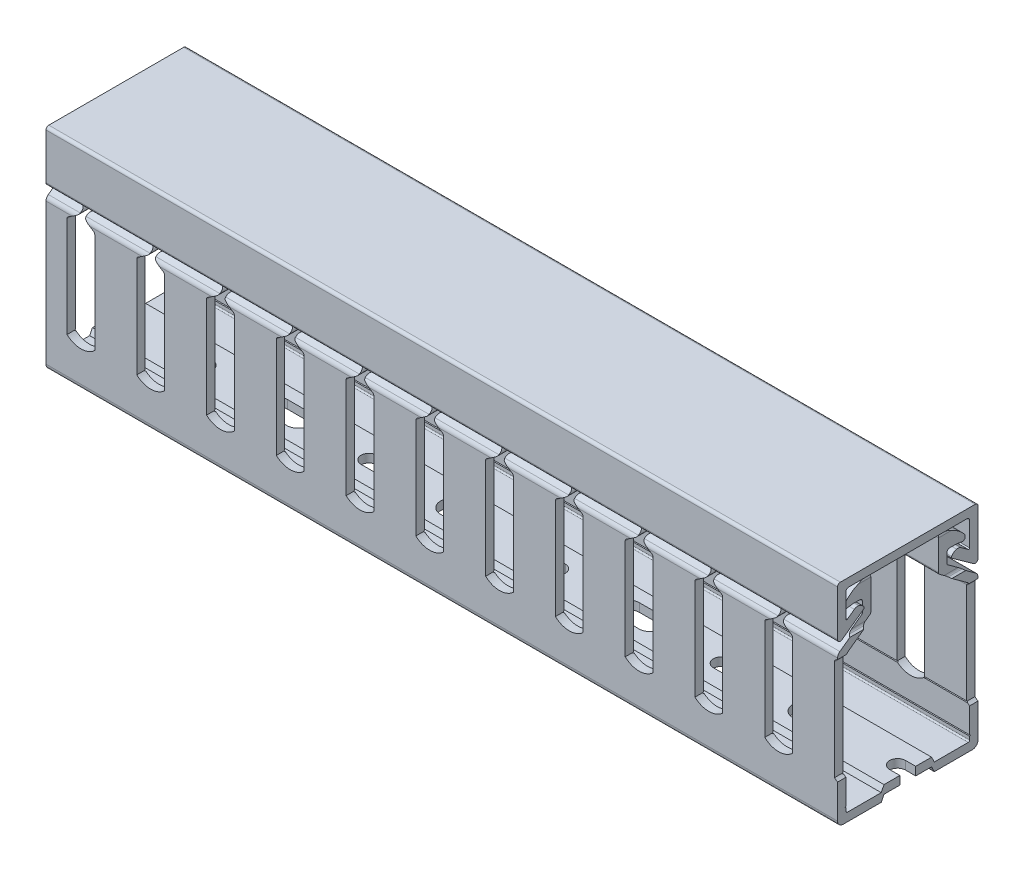
SolidWorks part; units mm, degrees
ref_plane "Alzado" through (0, 0, 0) normal (0, 0, 1) x (1, 0, 0)
ref_plane "Planta" through (0, 0, 0) normal (0, 1, 0) x (1, 0, 0)
ref_plane "Vista lateral" through (0, 0, 0) normal (1, 0, 0) x (0, 0, -1)
sketch "Croquis1" plane through (0, 0, 0) normal (1, 0, 0) x (0, 0, -1)
  line L0 (19.2861, 41.3685) -> (12.1583, 46.5609)
  line L1 (16.9056, 40.2266) -> (9.9464, 45.2924)
  line L2 (17.1611, 50.9204) -> (17.1611, 50.9657)
  line L3 (-7.5409, 0.7912) -> (-6.7469, 2.38)
  line L4 (-6.7469, 2.38) -> (-3.175, 2.38)
  line L5 (-7.5413, -1.5888) -> (-6.7469, 0)
  line L6 (-6.7469, 0) -> (-3.175, 0)
  line L7 (-7.5413, -1.5888) -> (-18.3513, -1.5888)
  line L8 (-3.175, 2.38) -> (3.175, 2.38)
  line L9 (-3.175, 0) -> (3.175, 0)
  line L10 (-17.5588, 10.0456) -> (-17.5588, 2.4512)
  line L11 (-17.162, 0.7912) -> (-7.5409, 0.7912)
  line L12 (-17.856, 2.2796) -> (-17.5588, 2.4512)
  line L13 (-17.856, 2.2796) -> (-17.5588, 2.1081)
  line L14 (-17.5588, 2.1081) -> (-17.5588, 1.1881)
  line L15 (-17.856, 10.2171) -> (-17.5588, 10.0456)
  line L16 (-17.856, 10.2171) -> (-17.5588, 10.3887)
  line L17 (17.5588, 10.0456) -> (17.5588, 2.4512)
  line L18 (17.5588, 2.1081) -> (17.5588, 1.1881)
  line L19 (17.856, 2.2796) -> (17.5588, 2.1081)
  line L20 (17.856, 2.2796) -> (17.5588, 2.4512)
  line L21 (17.856, 10.2171) -> (17.5588, 10.3887)
  line L22 (17.856, 10.2171) -> (17.5588, 10.0456)
  line L23 (17.5588, 38.9431) -> (17.5588, 10.3887)
  line L24 (19.9388, -0.0013) -> (19.9388, 40.0854)
  line L25 (12.0017, 46.8688) -> (12.0017, 49.624)
  line L26 (9.6198, 45.9342) -> (9.6198, 54.439)
  line L27 (14.842, 50.4074) -> (16.2738, 50.1687)
  line L28 (12.7954, 50.4177) -> (14.7167, 50.4177)
  line L29 (-19.2861, 41.3685) -> (-12.1583, 46.5609)
  line L30 (-16.9056, 40.2266) -> (-9.9464, 45.2924)
  line L31 (-9.6198, 45.9342) -> (-9.6198, 54.439)
  line L32 (-12.7954, 50.4177) -> (-14.7167, 50.4177)
  line L33 (-12.0017, 46.8688) -> (-12.0017, 49.624)
  line L34 (-14.842, 50.4074) -> (-16.2738, 50.1687)
  line L35 (-17.1611, 50.9204) -> (-17.1611, 50.9657)
  line L36 (-17.5588, 38.9431) -> (-17.5588, 10.3887)
  line L37 (-19.9388, -0.0013) -> (-19.9388, 40.0854)
  line L38 (3.175, 0) -> (6.7469, 0)
  line L39 (6.7469, 0) -> (7.5413, -1.5888)
  line L40 (7.5413, -1.5888) -> (18.3513, -1.5888)
  line L41 (17.162, 0.7912) -> (7.5413, 0.7912)
  line L42 (7.5413, 0.7912) -> (6.7469, 2.38)
  line L43 (6.7469, 2.38) -> (3.175, 2.38)
  arc A0 (-17.5588, 1.1881) -> (-17.162, 0.7912) centre (-17.162, 1.1881) ccw
  arc A1 (-19.9388, -0.0013) -> (-18.3513, -1.5888) centre (-18.3513, -0.0013) ccw
  arc A2 (17.162, 0.7912) -> (17.5588, 1.1881) centre (17.162, 1.1881) ccw
  arc A3 (18.3513, -1.5888) -> (19.9388, -0.0013) centre (18.3513, -0.0013) ccw
  arc A4 (19.9388, 40.0854) -> (19.2861, 41.3685) centre (18.3513, 40.0854) ccw
  arc A5 (17.5588, 38.9431) -> (16.9056, 40.2266) centre (15.9713, 38.9431) ccw
  arc A6 (12.0017, 46.8688) -> (12.1583, 46.5609) centre (12.3827, 46.8688) ccw
  arc A7 (9.6198, 45.9342) -> (9.9464, 45.2924) centre (10.4136, 45.9342) ccw
  arc A8 (12.7954, 50.4177) -> (12.0017, 49.624) centre (12.7954, 49.624) ccw
  arc A9 (10.688, 55.1838) -> (9.6198, 54.439) centre (10.4136, 54.439) ccw
  arc A10 (16.86, 51.7867) -> (10.688, 55.1838) centre (9.3251, 45.4023) ccw
  arc A11 (17.1611, 50.9657) -> (16.86, 51.7867) centre (15.8911, 50.9657) ccw
  arc A12 (16.2738, 50.1687) -> (17.1611, 50.9204) centre (16.3991, 50.9204) ccw
  arc A13 (14.842, 50.4074) -> (14.7167, 50.4177) centre (14.7167, 49.6557) ccw
  arc A14 (-9.9464, 45.2924) -> (-9.6198, 45.9342) centre (-10.4136, 45.9342) ccw
  arc A15 (-16.9056, 40.2266) -> (-17.5588, 38.9431) centre (-15.9713, 38.9431) ccw
  arc A16 (-19.2861, 41.3685) -> (-19.9388, 40.0854) centre (-18.3513, 40.0854) ccw
  arc A17 (-9.6198, 54.439) -> (-10.688, 55.1838) centre (-10.4136, 54.439) ccw
  arc A18 (-16.86, 51.7867) -> (-17.1611, 50.9657) centre (-15.8911, 50.9657) ccw
  arc A19 (-12.1583, 46.5609) -> (-12.0017, 46.8688) centre (-12.3827, 46.8688) ccw
  arc A20 (-12.0017, 49.624) -> (-12.7954, 50.4177) centre (-12.7954, 49.624) ccw
  arc A21 (-14.7167, 50.4177) -> (-14.842, 50.4074) centre (-14.7167, 49.6557) ccw
  arc A22 (-17.1611, 50.9204) -> (-16.2738, 50.1687) centre (-16.3991, 50.9204) ccw
  arc A23 (-10.688, 55.1838) -> (-16.86, 51.7867) centre (-9.3251, 45.4023) ccw
  point P92 (0, 0)
extrude "Saliente-Extruir1" add sketch "Croquis1" along normal mid plane 762
sketch "Croquis5" plane through (0, 2.38, 0) normal (0, 1, 0) x (1, 0, 0)
  line L157 (-379.0156, -3.2514) -> (-381, -3.2514)
  line L158 (-379.0156, 3.251) -> (-381, 3.251)
  line L159 (-335.6864, 3.251) -> (-329.3364, 3.251)
  line L160 (-335.6864, -3.2514) -> (-329.3364, -3.2514)
  line L161 (-235.6612, -3.2514) -> (-229.3112, -3.2514)
  line L162 (-235.6612, 3.251) -> (-229.3112, 3.251)
  line L163 (-285.6738, -3.2514) -> (-279.3238, -3.2514)
  line L164 (-285.6738, 3.251) -> (-279.3238, 3.251)
  line L165 (-185.6486, -3.2514) -> (-179.2986, -3.2514)
  line L166 (-185.6486, 3.251) -> (-182.1992, 3.251)
  line L167 (-309.2402, 2.2477) -> (-305.7446, 2.2477)
  line L168 (-309.2402, -2.2481) -> (-305.7446, -2.2481)
  line L169 (-355.7826, -2.2481) -> (-359.2782, -2.2481)
  line L170 (-355.7826, 2.2477) -> (-359.2782, 2.2477)
  line L171 (-259.2276, -2.2481) -> (-255.732, -2.2481)
  line L172 (-259.2276, 2.2477) -> (-255.732, 2.2477)
  line L173 (-209.215, -2.2481) -> (-205.7194, -2.2481)
  line L174 (-209.215, 2.2477) -> (-205.7194, 2.2477)
  line L188 (-398.7832, -0.0002) -> (-161.8215, -0.0002) construction
  arc A105 (-379.0156, -3.2514) -> (-379.0156, 3.251) centre (-379.0156, -0.0002) ccw
  arc A106 (-329.3364, -3.2514) -> (-329.3364, 3.251) centre (-329.3364, -0.0002) ccw
  arc A107 (-335.6864, 3.251) -> (-335.6864, -3.2514) centre (-335.6864, -0.0002) ccw
  circle A108 centre (-332.5114, -0.0002) radius 6.677
  circle A109 centre (-332.5114, -0.0002) radius 7.4708
  circle A110 centre (-232.4862, -0.0002) radius 6.677
  circle A111 centre (-232.4862, -0.0002) radius 7.4708
  arc A112 (-229.3112, -3.2514) -> (-229.3112, 3.251) centre (-229.3112, -0.0002) ccw
  arc A113 (-235.6612, 3.251) -> (-235.6612, -3.2514) centre (-235.6612, -0.0002) ccw
  arc A114 (-279.3238, -3.2514) -> (-279.3238, 3.251) centre (-279.3238, -0.0002) ccw
  arc A115 (-285.6738, 3.251) -> (-285.6738, -3.2514) centre (-285.6738, -0.0002) ccw
  arc A116 (-179.2986, -3.2514) -> (-178.0729, -3.0115) centre (-179.2986, -0.0002) ccw
  arc A117 (-185.6486, 3.251) -> (-185.6486, -3.2514) centre (-185.6486, -0.0002) ccw
  arc A118 (-309.2402, 2.2477) -> (-309.2402, -2.2481) centre (-309.2402, -0.0002) ccw
  arc A119 (-305.7446, -2.2481) -> (-305.7446, 2.2477) centre (-305.7446, -0.0002) ccw
  arc A120 (-359.2782, 2.2477) -> (-359.2782, -2.2481) centre (-359.2782, -0.0002) ccw
  arc A121 (-355.7826, -2.2481) -> (-355.7826, 2.2477) centre (-355.7826, -0.0002) ccw
  arc A122 (-255.732, -2.2481) -> (-255.732, 2.2477) centre (-255.732, -0.0002) ccw
  arc A123 (-259.2276, 2.2477) -> (-259.2276, -2.2481) centre (-259.2276, -0.0002) ccw
  arc A124 (-205.7194, -2.2481) -> (-205.7194, 2.2477) centre (-205.7194, -0.0002) ccw
  arc A125 (-209.215, 2.2477) -> (-209.215, -2.2481) centre (-209.215, -0.0002) ccw
  point P817 (-381, 3.251)
  point P818 (-381, -3.2514)
  point P820 (-359.2782, 2.2477)
  point P821 (-359.2782, -2.2481)
  point P823 (-361.5261, -0.0002)
  point P824 (-353.5347, -0.0002)
  point P826 (-285.6738, 3.251)
  point P827 (-285.6738, -3.2514)
  point P829 (-288.925, -0.0002)
  point P830 (-276.0726, -0.0002)
sketch "Croquis6" plane through (0, 2.38, 0) normal (0, 1, 0) x (1, 0, 0)
  line L5 (0, 0) -> (-149.8099, 0) construction
  line L6 (-382.9844, 0) -> (-379.0156, 0) construction
  line L7 (-382.9844, 3.25) -> (-379.0156, 3.25)
  line L8 (-382.9844, -3.25) -> (-379.0156, -3.25)
  line L10 (-381, 6.7469) -> (-381, -6.7469) construction
  line L11 (-355.7826, 0) -> (-359.2782, 0) construction
  line L12 (-355.7826, -2.25) -> (-359.2782, -2.25)
  line L13 (-355.7826, 2.25) -> (-359.2782, 2.25)
  line L14 (-305.7446, 0) -> (-309.2402, 0) construction
  line L15 (-305.7446, -2.25) -> (-309.2402, -2.25)
  line L16 (-305.7446, 2.25) -> (-309.2402, 2.25)
  line L17 (-255.7066, 0) -> (-259.2022, 0) construction
  line L18 (-255.7066, -2.25) -> (-259.2022, -2.25)
  line L19 (-255.7066, 2.25) -> (-259.2022, 2.25)
  line L20 (-205.6686, 0) -> (-209.1642, 0) construction
  line L21 (-205.6686, -2.25) -> (-209.1642, -2.25)
  line L22 (-205.6686, 2.25) -> (-209.1642, 2.25)
  line L23 (-155.6306, 0) -> (-159.1262, 0) construction
  line L24 (-155.6306, -2.25) -> (-159.1262, -2.25)
  line L25 (-155.6306, 2.25) -> (-159.1262, 2.25)
  line L26 (-105.5926, 0) -> (-109.0882, 0) construction
  line L27 (-105.5926, -2.25) -> (-109.0882, -2.25)
  line L28 (-105.5926, 2.25) -> (-109.0882, 2.25)
  line L29 (-55.5546, 0) -> (-59.0502, 0) construction
  line L30 (-55.5546, -2.25) -> (-59.0502, -2.25)
  line L31 (-55.5546, 2.25) -> (-59.0502, 2.25)
  line L32 (-5.5166, 0) -> (-9.0122, 0) construction
  line L33 (-5.5166, -2.25) -> (-9.0122, -2.25)
  line L34 (-5.5166, 2.25) -> (-9.0122, 2.25)
  line L35 (44.5214, 0) -> (41.0258, 0) construction
  line L36 (44.5214, -2.25) -> (41.0258, -2.25)
  line L37 (44.5214, 2.25) -> (41.0258, 2.25)
  line L38 (94.5594, 0) -> (91.0638, 0) construction
  line L39 (94.5594, -2.25) -> (91.0638, -2.25)
  line L40 (94.5594, 2.25) -> (91.0638, 2.25)
  line L41 (144.5974, 0) -> (141.1018, 0) construction
  line L42 (144.5974, -2.25) -> (141.1018, -2.25)
  line L43 (144.5974, 2.25) -> (141.1018, 2.25)
  line L44 (194.6354, 0) -> (191.1398, 0) construction
  line L45 (194.6354, -2.25) -> (191.1398, -2.25)
  line L46 (194.6354, 2.25) -> (191.1398, 2.25)
  line L47 (244.6734, 0) -> (241.1778, 0) construction
  line L48 (244.6734, -2.25) -> (241.1778, -2.25)
  line L49 (244.6734, 2.25) -> (241.1778, 2.25)
  line L50 (294.7114, 0) -> (291.2158, 0) construction
  line L51 (294.7114, -2.25) -> (291.2158, -2.25)
  line L52 (294.7114, 2.25) -> (291.2158, 2.25)
  line L53 (344.7494, 0) -> (341.2538, 0) construction
  line L54 (344.7494, -2.25) -> (341.2538, -2.25)
  line L55 (344.7494, 2.25) -> (341.2538, 2.25)
  line L56 (394.7874, 0) -> (391.2918, 0) construction
  line L57 (394.7874, -2.25) -> (391.2918, -2.25)
  line L58 (394.7874, 2.25) -> (391.2918, 2.25)
  arc A3 (-382.9844, 3.25) -> (-382.9844, -3.25) centre (-382.9844, 0) ccw
  arc A4 (-379.0156, -3.25) -> (-379.0156, 3.25) centre (-379.0156, 0) ccw
  arc A5 (-355.7826, -2.25) -> (-355.7826, 2.25) centre (-355.7826, 0) ccw
  arc A6 (-359.2782, 2.25) -> (-359.2782, -2.25) centre (-359.2782, 0) ccw
  arc A7 (-305.7446, -2.25) -> (-305.7446, 2.25) centre (-305.7446, 0) ccw
  arc A8 (-309.2402, 2.25) -> (-309.2402, -2.25) centre (-309.2402, 0) ccw
  arc A9 (-255.7066, -2.25) -> (-255.7066, 2.25) centre (-255.7066, 0) ccw
  arc A10 (-259.2022, 2.25) -> (-259.2022, -2.25) centre (-259.2022, 0) ccw
  arc A11 (-205.6686, -2.25) -> (-205.6686, 2.25) centre (-205.6686, 0) ccw
  arc A12 (-209.1642, 2.25) -> (-209.1642, -2.25) centre (-209.1642, 0) ccw
  arc A13 (-155.6306, -2.25) -> (-155.6306, 2.25) centre (-155.6306, 0) ccw
  arc A14 (-159.1262, 2.25) -> (-159.1262, -2.25) centre (-159.1262, 0) ccw
  arc A15 (-105.5926, -2.25) -> (-105.5926, 2.25) centre (-105.5926, 0) ccw
  arc A16 (-109.0882, 2.25) -> (-109.0882, -2.25) centre (-109.0882, 0) ccw
  arc A17 (-55.5546, -2.25) -> (-55.5546, 2.25) centre (-55.5546, 0) ccw
  arc A18 (-59.0502, 2.25) -> (-59.0502, -2.25) centre (-59.0502, 0) ccw
  arc A19 (-5.5166, -2.25) -> (-5.5166, 2.25) centre (-5.5166, 0) ccw
  arc A20 (-9.0122, 2.25) -> (-9.0122, -2.25) centre (-9.0122, 0) ccw
  arc A21 (44.5214, -2.25) -> (44.5214, 2.25) centre (44.5214, 0) ccw
  arc A22 (41.0258, 2.25) -> (41.0258, -2.25) centre (41.0258, 0) ccw
  arc A23 (94.5594, -2.25) -> (94.5594, 2.25) centre (94.5594, 0) ccw
  arc A24 (91.0638, 2.25) -> (91.0638, -2.25) centre (91.0638, 0) ccw
  arc A25 (144.5974, -2.25) -> (144.5974, 2.25) centre (144.5974, 0) ccw
  arc A26 (141.1018, 2.25) -> (141.1018, -2.25) centre (141.1018, 0) ccw
  arc A27 (194.6354, -2.25) -> (194.6354, 2.25) centre (194.6354, 0) ccw
  arc A28 (191.1398, 2.25) -> (191.1398, -2.25) centre (191.1398, 0) ccw
  arc A29 (244.6734, -2.25) -> (244.6734, 2.25) centre (244.6734, 0) ccw
  arc A30 (241.1778, 2.25) -> (241.1778, -2.25) centre (241.1778, 0) ccw
  arc A31 (294.7114, -2.25) -> (294.7114, 2.25) centre (294.7114, 0) ccw
  arc A32 (291.2158, 2.25) -> (291.2158, -2.25) centre (291.2158, 0) ccw
  arc A33 (344.7494, -2.25) -> (344.7494, 2.25) centre (344.7494, 0) ccw
  arc A34 (341.2538, 2.25) -> (341.2538, -2.25) centre (341.2538, 0) ccw
  arc A35 (394.7874, -2.25) -> (394.7874, 2.25) centre (394.7874, 0) ccw
  arc A36 (391.2918, 2.25) -> (391.2918, -2.25) centre (391.2918, 0) ccw
  point P0 (-381, 0)
  point P8 (-357.5304, 0)
  point P26 (-307.4924, 0)
  point P33 (-257.4544, 0)
  point P40 (-207.4164, 0)
  point P47 (-157.3784, 0)
  point P54 (-107.3404, 0)
  point P61 (-57.3024, 0)
  point P68 (-7.2644, 0)
  point P75 (42.7736, 0)
  point P82 (92.8116, 0)
  point P89 (142.8496, 0)
  point P96 (192.8876, 0)
  point P103 (242.9256, 0)
  point P110 (292.9636, 0)
  point P117 (343.0016, 0)
  point P124 (393.0396, 0)
  dimension "D1" = 6.5
  dimension "D3" = 4.5
  dimension "D2" = 3.9687
  dimension "D4" = 3.4957
  dimension "D5" = 19.7374
  dimension "D7" = 50.038
  dimension "D6" = 16
extrude "Cortar-Extruir3" cut sketch "Croquis6" against normal through all
sketch "Croquis7" plane through (0, 2.38, 0) normal (0, 1, 0) x (1, 0, 0)
  line L0 (431.9082, 0) -> (-431.9082, 0) construction
  line L1 (-335.6864, 0) -> (-329.3364, 0) construction
  line L2 (-335.6864, 3.2512) -> (-329.3364, 3.2512)
  line L3 (-335.6864, -3.2512) -> (-329.3364, -3.2512)
  line L4 (-381, 17.162) -> (-381, 7.5413) construction
  line L5 (-285.6738, 0) -> (-279.3238, 0) construction
  line L6 (-285.6738, 3.2512) -> (-279.3238, 3.2512)
  line L7 (-285.6738, -3.2512) -> (-279.3238, -3.2512)
  line L8 (-235.6612, 0) -> (-229.3112, 0) construction
  line L9 (-235.6612, 3.2512) -> (-229.3112, 3.2512)
  line L10 (-235.6612, -3.2512) -> (-229.3112, -3.2512)
  line L11 (-185.6486, 0) -> (-179.2986, 0) construction
  line L12 (-185.6486, 3.2512) -> (-179.2986, 3.2512)
  line L13 (-185.6486, -3.2512) -> (-179.2986, -3.2512)
  line L14 (-135.636, 0) -> (-129.286, 0) construction
  line L15 (-135.636, 3.2512) -> (-129.286, 3.2512)
  line L16 (-135.636, -3.2512) -> (-129.286, -3.2512)
  line L17 (-85.6234, 0) -> (-79.2734, 0) construction
  line L18 (-85.6234, 3.2512) -> (-79.2734, 3.2512)
  line L19 (-85.6234, -3.2512) -> (-79.2734, -3.2512)
  line L20 (-35.6108, 0) -> (-29.2608, 0) construction
  line L21 (-35.6108, 3.2512) -> (-29.2608, 3.2512)
  line L22 (-35.6108, -3.2512) -> (-29.2608, -3.2512)
  line L23 (14.4018, 0) -> (20.7518, 0) construction
  line L24 (14.4018, 3.2512) -> (20.7518, 3.2512)
  line L25 (14.4018, -3.2512) -> (20.7518, -3.2512)
  line L26 (64.4144, 0) -> (70.7644, 0) construction
  line L27 (64.4144, 3.2512) -> (70.7644, 3.2512)
  line L28 (64.4144, -3.2512) -> (70.7644, -3.2512)
  line L29 (114.427, 0) -> (120.777, 0) construction
  line L30 (114.427, 3.2512) -> (120.777, 3.2512)
  line L31 (114.427, -3.2512) -> (120.777, -3.2512)
  line L32 (164.4396, 0) -> (170.7896, 0) construction
  line L33 (164.4396, 3.2512) -> (170.7896, 3.2512)
  line L34 (164.4396, -3.2512) -> (170.7896, -3.2512)
  line L35 (214.4522, 0) -> (220.8022, 0) construction
  line L36 (214.4522, 3.2512) -> (220.8022, 3.2512)
  line L37 (214.4522, -3.2512) -> (220.8022, -3.2512)
  line L38 (264.4648, 0) -> (270.8148, 0) construction
  line L39 (264.4648, 3.2512) -> (270.8148, 3.2512)
  line L40 (264.4648, -3.2512) -> (270.8148, -3.2512)
  line L41 (314.4774, 0) -> (320.8274, 0) construction
  line L42 (314.4774, 3.2512) -> (320.8274, 3.2512)
  line L43 (314.4774, -3.2512) -> (320.8274, -3.2512)
  line L44 (364.49, 0) -> (370.84, 0) construction
  line L45 (364.49, 3.2512) -> (370.84, 3.2512)
  line L46 (364.49, -3.2512) -> (370.84, -3.2512)
  arc A0 (-335.6864, 3.2512) -> (-335.6864, -3.2512) centre (-335.6864, 0) ccw
  arc A1 (-329.3364, -3.2512) -> (-329.3364, 3.2512) centre (-329.3364, 0) ccw
  arc A2 (-285.6738, 3.2512) -> (-285.6738, -3.2512) centre (-285.6738, 0) ccw
  arc A3 (-279.3238, -3.2512) -> (-279.3238, 3.2512) centre (-279.3238, 0) ccw
  arc A4 (-235.6612, 3.2512) -> (-235.6612, -3.2512) centre (-235.6612, 0) ccw
  arc A5 (-229.3112, -3.2512) -> (-229.3112, 3.2512) centre (-229.3112, 0) ccw
  arc A6 (-185.6486, 3.2512) -> (-185.6486, -3.2512) centre (-185.6486, 0) ccw
  arc A7 (-179.2986, -3.2512) -> (-179.2986, 3.2512) centre (-179.2986, 0) ccw
  arc A8 (-135.636, 3.2512) -> (-135.636, -3.2512) centre (-135.636, 0) ccw
  arc A9 (-129.286, -3.2512) -> (-129.286, 3.2512) centre (-129.286, 0) ccw
  arc A10 (-85.6234, 3.2512) -> (-85.6234, -3.2512) centre (-85.6234, 0) ccw
  arc A11 (-79.2734, -3.2512) -> (-79.2734, 3.2512) centre (-79.2734, 0) ccw
  arc A12 (-35.6108, 3.2512) -> (-35.6108, -3.2512) centre (-35.6108, 0) ccw
  arc A13 (-29.2608, -3.2512) -> (-29.2608, 3.2512) centre (-29.2608, 0) ccw
  arc A14 (14.4018, 3.2512) -> (14.4018, -3.2512) centre (14.4018, 0) ccw
  arc A15 (20.7518, -3.2512) -> (20.7518, 3.2512) centre (20.7518, 0) ccw
  arc A16 (64.4144, 3.2512) -> (64.4144, -3.2512) centre (64.4144, 0) ccw
  arc A17 (70.7644, -3.2512) -> (70.7644, 3.2512) centre (70.7644, 0) ccw
  arc A18 (114.427, 3.2512) -> (114.427, -3.2512) centre (114.427, 0) ccw
  arc A19 (120.777, -3.2512) -> (120.777, 3.2512) centre (120.777, 0) ccw
  arc A20 (164.4396, 3.2512) -> (164.4396, -3.2512) centre (164.4396, 0) ccw
  arc A21 (170.7896, -3.2512) -> (170.7896, 3.2512) centre (170.7896, 0) ccw
  arc A22 (214.4522, 3.2512) -> (214.4522, -3.2512) centre (214.4522, 0) ccw
  arc A23 (220.8022, -3.2512) -> (220.8022, 3.2512) centre (220.8022, 0) ccw
  arc A24 (264.4648, 3.2512) -> (264.4648, -3.2512) centre (264.4648, 0) ccw
  arc A25 (270.8148, -3.2512) -> (270.8148, 3.2512) centre (270.8148, 0) ccw
  arc A26 (314.4774, 3.2512) -> (314.4774, -3.2512) centre (314.4774, 0) ccw
  arc A27 (320.8274, -3.2512) -> (320.8274, 3.2512) centre (320.8274, 0) ccw
  arc A28 (364.49, 3.2512) -> (364.49, -3.2512) centre (364.49, 0) ccw
  arc A29 (370.84, -3.2512) -> (370.84, 3.2512) centre (370.84, 0) ccw
  point P4 (0, 0)
  point P9 (-332.5114, 0)
  point P16 (-282.4988, 0)
  point P28 (-232.4862, 0)
  point P35 (-182.4736, 0)
  point P42 (-132.461, 0)
  point P49 (-82.4484, 0)
  point P56 (-32.4358, 0)
  point P63 (17.5768, 0)
  point P70 (67.5894, 0)
  point P77 (117.602, 0)
  point P84 (167.6146, 0)
  point P91 (217.6272, 0)
  point P98 (267.6398, 0)
  point P105 (317.6524, 0)
  point P112 (367.665, 0)
  dimension "D5" = 50.0126
  dimension "D1" = 6.5024
  dimension "D2" = 6.35
  dimension "D3" = 45.3136
  dimension "D4" = 15
extrude "Cortar-Extruir4" cut sketch "Croquis7" against normal through all
sketch "Croquis4" plane through (0, 0, 19.9388) normal (0, 0, 1) x (1, 0, 0)
  line L0 (-375.031, 23.9974) -> (-367.157, 23.9974) construction
  line L1 (-371.094, 23.9974) -> (-371.094, 31.3497) construction
  line L2 (-367.157, 23.9974) -> (-355.219, 23.9974) construction
  line L3 (-356.0128, 55.2327) -> (-366.3633, 55.2327)
  line L4 (-369.9565, 42.2005) -> (-367.4745, 43.7644)
  line L5 (-369.9565, 40.9305) -> (-367.4745, 39.3666)
  line L6 (-367.157, 54.439) -> (-367.157, 44.3994)
  line L7 (-367.157, 38.7316) -> (-367.157, 23.9974)
  line L8 (-361.188, 23.9974) -> (-361.188, 33.0481) construction
  line L9 (-355.219, 38.7316) -> (-355.219, 23.9974)
  line L10 (-352.4195, 40.9305) -> (-354.9015, 39.3666)
  line L11 (-352.4195, 42.2005) -> (-354.9015, 43.7644)
  line L12 (-355.219, 54.439) -> (-355.219, 44.3994)
  line L13 (-375.031, 23.9974) -> (-375.031, 10.2476)
  line L14 (-375.031, 10.2476) -> (-367.157, 10.2476) construction
  line L15 (381, -1.5888) -> (-381, -1.5888) construction
  line L17 (-367.157, 10.2476) -> (-367.157, 23.9974)
  line L47 (-366.3633, 55.2327) -> (-375.8248, 55.2327)
  line L99 (-375.031, 38.7316) -> (-375.031, 23.9974)
  line L100 (-375.031, 54.439) -> (-375.031, 44.3994)
  line L103 (-372.2315, 40.9305) -> (-374.7135, 39.3666)
  line L104 (-372.2315, 42.2005) -> (-374.7135, 43.7644)
  line L106 (-381, 55.2327) -> (-375.8248, 55.2327)
  line L107 (-381, 55.2327) -> (-381, -1.5888)
  arc A0 (-367.157, 54.439) -> (-366.3633, 55.2327) centre (-366.3633, 54.439) cw
  arc A1 (-367.157, 44.3994) -> (-367.4745, 43.7644) centre (-367.9508, 44.3994) cw
  arc A2 (-367.4745, 39.3666) -> (-367.157, 38.7316) centre (-367.9508, 38.7316) cw
  arc A3 (-369.9565, 40.9305) -> (-369.9565, 42.2005) centre (-369.4803, 41.5655) cw
  arc A4 (-354.9015, 39.3666) -> (-355.219, 38.7316) centre (-354.4253, 38.7316) ccw
  arc A5 (-352.4195, 40.9305) -> (-352.4195, 42.2005) centre (-352.8957, 41.5655) ccw
  arc A6 (-355.219, 44.3994) -> (-354.9015, 43.7644) centre (-354.4253, 44.3994) ccw
  arc A7 (-355.219, 54.439) -> (-356.0128, 55.2327) centre (-356.0128, 54.439) ccw
  arc A37 (-375.031, 10.2476) -> (-367.157, 10.2476) centre (-371.094, 14.464) ccw
  arc A79 (-372.2315, 40.9305) -> (-372.2315, 42.2005) centre (-372.7077, 41.5655) ccw
  arc A80 (-374.7135, 39.3666) -> (-375.031, 38.7316) centre (-374.2372, 38.7316) ccw
  arc A81 (-375.031, 44.3994) -> (-374.7135, 43.7644) centre (-374.2372, 44.3994) ccw
  arc A82 (-375.031, 54.439) -> (-375.8248, 55.2327) centre (-375.8248, 54.439) ccw
  point P0 (-381, 55.2327)
  point P18 (-381, 55.2327)
  point P33 (-361.188, 55.2327)
  line M606 (381, 40.0854) -> (-381, 40.0854)
  dimension "D1" = 11.8364
  dimension "D2" = 56.8215
extrude "Cortar-Extruir2" cut sketch "Croquis4" against normal blind 762 contours L103 A80 L99 L13 A37 L17 L7 A2 L5 M606 | A82 L100 A81 L104 A79 L103 L5 A3 L4 A1 L6 A0 L47 M606 region at (-371.094, 48.6138, 19.9388) region at (-371.094, 24.5427, 19.9388)
pattern_linear "MatrizL1" count 39 spacing 19.812 along (1, 0, 0) of "Cortar-Extruir2"
sketch "Croquis2" plane through (381, 0, 0) normal (1, 0, 0) x (0, 0, -1)
  line L0 (-19.1454, 58.3552) -> (19.1454, 58.3552)
  line L1 (-16.7656, 55.9752) -> (16.7656, 55.9752)
  line L2 (19.9392, 44.6261) -> (19.9392, 57.5615)
  line L3 (18.6821, 43.9816) -> (12.5201, 48.4108)
  line L4 (17.5594, 55.1813) -> (17.5577, 48.4602)
  line L5 (17.1554, 48.254) -> (15.1574, 49.6901)
  line L6 (-19.9392, 44.6261) -> (-19.9392, 57.5615)
  line L7 (-18.6821, 43.9816) -> (-12.5201, 48.4108)
  line L8 (-17.5594, 55.1813) -> (-17.5577, 48.4602)
  line L9 (-17.1554, 48.254) -> (-15.1574, 49.6901)
  line L10 (0, 0) -> (0, 58.3552) construction
  line L11 (7.5413, -1.5888) -> (18.3513, -1.5888) construction
  arc A0 (17.1554, 48.254) -> (17.5577, 48.4602) centre (17.3037, 48.4602) ccw
  arc A1 (13.8793, 49.9491) -> (12.4217, 48.9257) centre (14.3995, 47.6586) ccw
  arc A2 (15.1574, 49.6901) -> (13.8793, 49.9491) centre (14.2309, 48.4011) ccw
  arc A3 (12.4217, 48.9257) -> (12.5201, 48.4108) centre (12.7425, 48.7202) ccw
  arc A4 (18.6821, 43.9816) -> (19.9392, 44.6261) centre (19.1454, 44.6261) ccw
  arc A5 (19.9392, 57.5615) -> (19.1454, 58.3552) centre (19.1454, 57.5615) ccw
  arc A6 (17.5594, 55.1813) -> (16.7656, 55.9752) centre (16.7656, 55.1815) ccw
  arc A7 (-19.9392, 44.6261) -> (-18.6821, 43.9816) centre (-19.1454, 44.6261) ccw
  arc A8 (-13.8793, 49.9491) -> (-15.1574, 49.6901) centre (-14.2309, 48.4011) ccw
  arc A9 (-12.5201, 48.4108) -> (-12.4217, 48.9257) centre (-12.7425, 48.7202) ccw
  arc A10 (-12.4217, 48.9257) -> (-13.8793, 49.9491) centre (-14.3995, 47.6586) ccw
  arc A11 (-17.5577, 48.4602) -> (-17.1554, 48.254) centre (-17.3037, 48.4602) ccw
  arc A12 (-16.7656, 55.9752) -> (-17.5594, 55.1813) centre (-16.7656, 55.1815) ccw
  arc A13 (-19.1454, 58.3552) -> (-19.9392, 57.5615) centre (-19.1454, 57.5615) ccw
  point P41 (0, 58.3552)
  dimension "D1" = 59.944
extrude "Saliente-Extruir2" add sketch "Croquis2" against normal up to surface (762 mm away) separate body up to face at (-381, 26.5287, -13.9522)
sketch "Croquis8" plane through (0, 58.3552, 0) normal (0, 1, 0) x (1, 0, 0)
  line L0 (-381, -19.9392) -> (381, -19.9392) construction
  line L1 (-381, 19.9392) -> (-156.24, 19.9392)
  line L2 (-381, 19.9392) -> (-381, -19.9392)
  line L3 (-381, -19.9392) -> (-156.24, -19.9392)
  line L4 (-156.24, 19.9392) -> (-156.24, -19.9392)
  dimension "D1" = 224.76
extrude "Cortar-Extruir5" cut sketch "Croquis8" against normal through all flip side to cut
